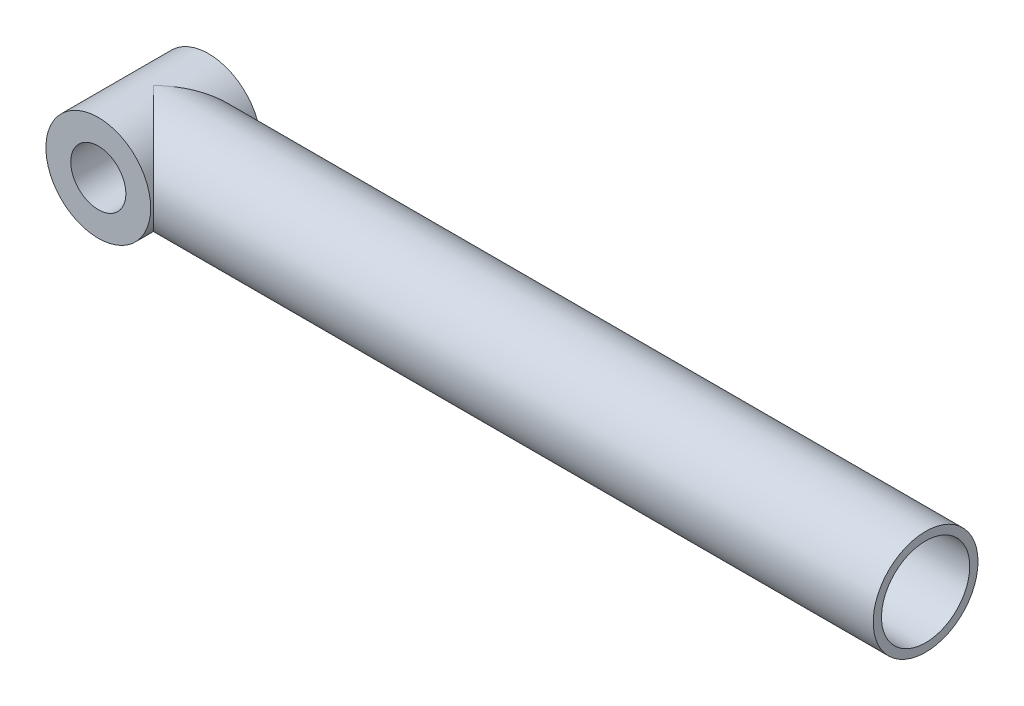
SolidWorks part; units mm, degrees
ref_plane "Front Plane" through (0, 0, 0) normal (0, 0, 1) x (1, 0, 0)
ref_plane "Top Plane" through (0, 0, 0) normal (0, 1, 0) x (1, 0, 0)
ref_plane "Right Plane" through (0, 0, 0) normal (1, 0, 0) x (0, 0, -1)
other "Configuration Table"
sketch "Sketch1" plane through (0, 0, 0) normal (0, 0, 1) x (1, 0, 0)
  circle A1 centre (0, 0) radius 47.5
  dimension "D2" = 95
extrude "Boss-Extrude1" add sketch "Sketch1" along normal blind 100
sketch3d "3DSketch1" plane through (0, 0, 0) normal (0, 0, 1) x (1, 0, 0)
  dimension "D1" = 700
sketch "Sketch2" plane through (700, 0, 0) normal (1, 0, 0) x (0, 0, -1)
  circle A0 centre (-50, 0) radius 47.5
  circle A1 centre (-50, 0) radius 40
  dimension "D3" = 95
  dimension "D4" = 80
extrude "Boss-Extrude2" add sketch "Sketch2" against normal up to surface (652.5 mm away) up to face at (47.5, 0, 100)
ref_plane "Plane1" through (50, 0, 0) normal (1, 0, 0) x (0, 0, -1)
sketch "Sketch3" plane through (50, 0, 0) normal (1, 0, 0) x (0, 0, -1)
  circle A0 centre (-50, 0) radius 40
extrude "Boss-Extrude4" add sketch "Sketch3" against normal up to surface (97.5 mm away) up to face at (47.5, 0, 50)
sketch "Sketch4" plane through (0, 0, 0) normal (0, 0, -1) x (-1, 0, 0)
  circle A0 centre (0, 0) radius 25
  dimension "D1" = 50
extrude "Cut-Extrude1" cut sketch "Sketch4" against normal up to surface (100 mm away) up to face at (47.5, 0, 100)
ref_point "Point1"
ref_point "Point2"
ref_axis "Axis1" through (0, 0, 50) along (1, 0, 0)
ref_axis "Axis2" through (0, 0, 100) along (0, 0, -1)
ref_plane "Plane2" through (0, 0, 0) normal (0, -1, 0) x (1, 0, 0)
